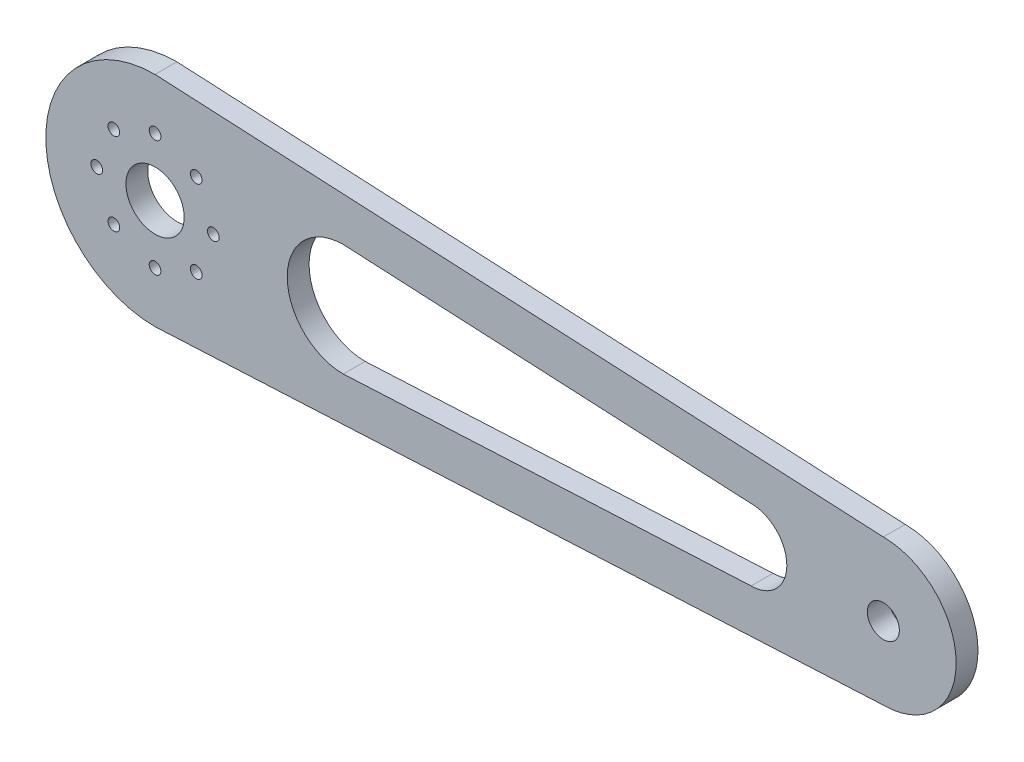
SolidWorks part; units mm, degrees
material "Pin"
ref_plane "Plan de face" through (0, 0, 0) normal (0, 0, 1) x (1, 0, 0)
ref_plane "Plan de dessus" through (0, 0, 0) normal (0, 1, 0) x (1, 0, 0)
ref_plane "Plan de droite" through (0, 0, 0) normal (1, 0, 0) x (0, 0, -1)
sketch "Esquisse1" plane through (0, 0, 0) normal (0, 0, 1) x (1, 0, 0)
  line L0 (0, -15) -> (100, -10)
  line L1 (0, 15) -> (100, 10)
  line L2 (25.8501, 7.7) -> (81.8501, 4.9)
  line L3 (25.8501, -7.7) -> (81.8501, -4.9)
  arc A0 (0, 15) -> (0, -15) centre (0, 0) ccw
  circle A5 centre (5.6569, 5.6569) radius 0.8
  circle A6 centre (8, 0) radius 0.8
  circle A7 centre (5.6569, -5.6569) radius 0.8
  circle A8 centre (0, -8) radius 0.8
  arc A9 (100, -10) -> (100, 10) centre (100, 0) ccw
  circle A10 centre (100, 0) radius 2.2
  circle A11 centre (0, 0) radius 4
  arc A12 (25.8501, 7.7) -> (25.8501, -7.7) centre (25.8501, 0) ccw
  arc A13 (81.8501, -4.9) -> (81.8501, 4.9) centre (81.8501, 0) ccw
  circle A14 centre (-5.6569, -5.6569) radius 0.8
  circle A15 centre (-8, 0) radius 0.8
  circle A16 centre (-5.6569, 5.6569) radius 0.8
  circle A17 centre (0, 8) radius 0.8
  point P14 (0, 0)
  point P23 (0, 0)
  point P31 (0, 0)
  point P35 (0, 0)
  point P36 (110, 0)
  point P37 (0, 0)
  point P38 (0, 0)
  dimension "D1" = 30
  dimension "D6" = 1.6
  dimension "D9" = 10
  dimension "D11" = 4.4
  dimension "D12" = 8
  dimension "D13" = 7.7
  dimension "D14" = 4.9
  dimension "D5" = 8
  dimension "D7" = 5.6569
  dimension "D8" = 8
  dimension "D10" = 100
  dimension "D15" = 6
  dimension "D16" = 6
  dimension "D17" = 6
  dimension "D18" = 6
extrude "Boss.-Extru.1" add sketch "Esquisse1" along normal blind 1.5 and the other way blind 1.5
